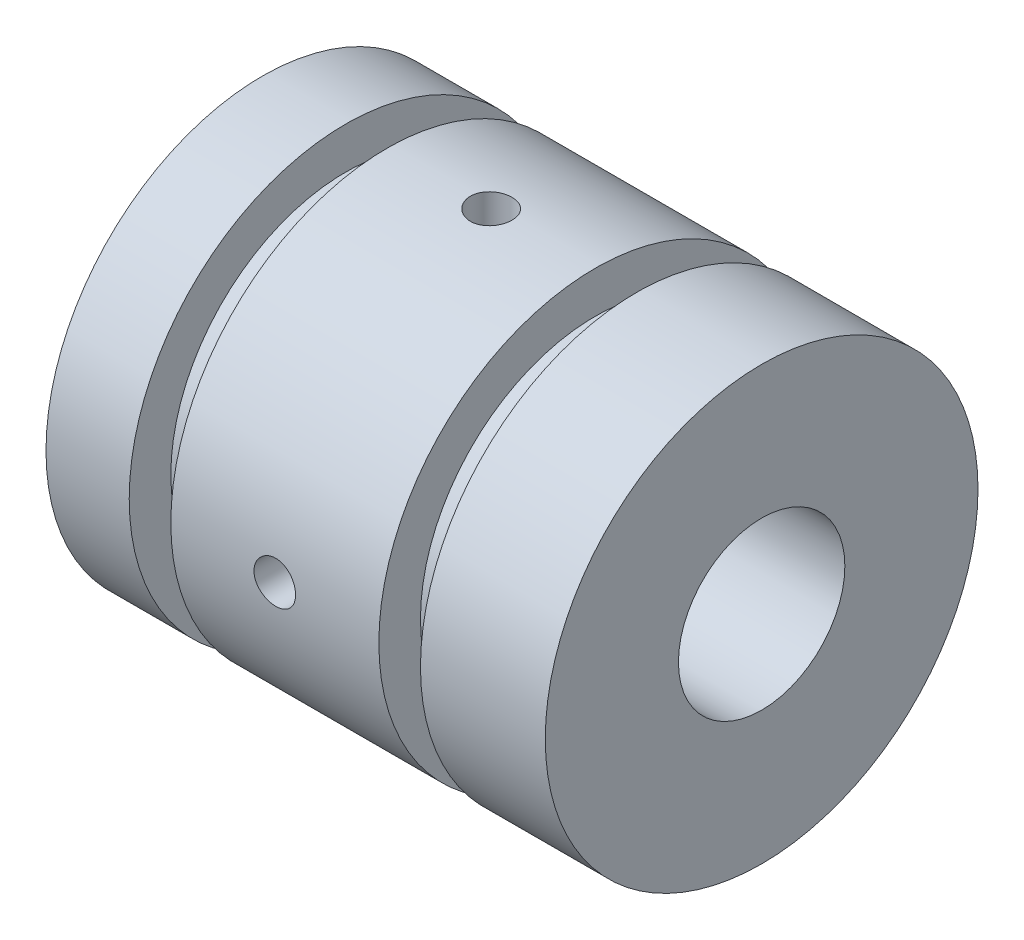
SolidWorks part; units mm, degrees
ref_plane "Front Plane" through (0, 0, 0) normal (0, 0, 1) x (1, 0, 0)
ref_plane "Top Plane" through (0, 0, 0) normal (0, 1, 0) x (1, 0, 0)
ref_plane "Right Plane" through (0, 0, 0) normal (1, 0, 0) x (0, 0, -1)
sketch "Sketch1" plane through (0, 0, 0) normal (0, 0, 1) x (1, 0, 0)
  line L0 (0, 0) -> (0, 26)
  line L1 (0, 26) -> (10, 26)
  line L2 (10, 26) -> (10, 21)
  line L3 (10, 21) -> (15, 21)
  line L4 (15, 21) -> (15, 26)
  line L5 (15, 26) -> (40, 26)
  line L6 (40, 26) -> (40, 21)
  line L7 (40, 21) -> (45, 21)
  line L8 (45, 21) -> (45, 26)
  line L9 (45, 26) -> (60, 26)
  line L10 (60, 26) -> (60, 45)
  line L11 (60, 45) -> (80, 45)
  line L12 (80, 45) -> (80, 0)
  line L13 (80, 0) -> (0, 0)
  line L14 (0, 0) -> (192.5132, 0) construction
  dimension "D1" = 80
  dimension "D2" = 26
  dimension "D3" = 10
  dimension "D4" = 25
  dimension "D5" = 15
  dimension "D6" = 5
  dimension "D7" = 45
  dimension "D8" = 5
revolve "Revolve1" add sketch "Sketch1" angle 360 about L14
sketch "Sketch2" plane through (0, 0, 0) normal (-1, 0, 0) x (0, 0, 1)
  circle A0 centre (0, 0) radius 20
  dimension "D1" = 40
extrude "Cut-Extrude2" cut sketch "Sketch2" against normal blind 10
hole_wizard "1/8 (0.125) Diameter Hole1" positions "Sketch4" profile "Sketch5" hole size "1/8" standard "ANSI Inch"
sketch "Sketch4" plane through (10, 0, 0) normal (-1, 0, 0) x (0, 0, 1)
  point P0 (15.1447, 0)
  point P6 (0.1447, -15)
  point P7 (-14.8553, 0)
  point P8 (0.1447, 15)
  point P9 (0, 0)
  dimension "D2" = 15
  dimension "D1" = 4
sketch "Sketch5" plane through (10, 0, 15.1447) normal (0, 1, 0) x (0, 0, 1)
  line L0 (0, 0) -> (0, 7.9539)
  line L1 (0, 7.9539) -> (1.5875, 7)
  line L2 (1.5875, 7) -> (1.5875, 0)
  line L5 (1.5875, 0) -> (0, 0)
  line L10 (0, 7.9539) -> (-1.5875, 7) construction
  line L11 (0, -6.35) -> (0, 107.95) construction
  dimension "Hole Dia." = 3.175
  dimension "Hole Depth" = 7
  dimension "Drill Angle" = 118
sketch "Sketch6" plane through (10, 0, 0) normal (-1, 0, 0) x (0, 0, 1)
  circle A0 centre (0, 0) radius 10
  dimension "D1" = 20
extrude "Cut-Extrude3" cut sketch "Sketch6" against normal blind 50
ref_axis "Axis1" through (40, 0, 0) along (-1, 0, 0)
ref_plane "Plane1" through (0, 0, 26) normal (0, 0, 1) x (1, 0, 0)
hole_wizard "1/2 (0.5) Diameter Hole1" positions "Sketch8" profile "Sketch9" hole size "1/2" standard "ANSI Inch" end condition up to next
sketch "Sketch8" plane through (80, 0, 0) normal (1, 0, 0) x (0, 0, -1)
  point P0 (0, 0)
sketch "Sketch9" plane through (80, 0, 0) normal (0, 1, 0) x (0, 0, -1)
  line L0 (0, 0) -> (0, 20)
  line L1 (0, 20) -> (6.35, 20)
  line L2 (6.35, 20) -> (6.35, 0)
  line L5 (6.35, 0) -> (0, 0)
  line L11 (0, -6.35) -> (0, 107.95) construction
  dimension "Thru Hole Dia." = 12.7
  dimension "Thru Hole Depth" = 20
sketch "Sketch10" plane through (0, -26, 26) normal (0, 0, 1) x (1, 0, 0)
  line L0 (15, 47) -> (15, 5) construction
  line L1 (40, 26) -> (15, 26) construction
  circle A0 centre (27.4918, 26) radius 2.5
  dimension "D1" = 5
  dimension "D2" = 12.4918
extrude "Cut-Extrude8" cut sketch "Sketch10" against normal blind 5
ref_plane "Plane2" through (0, 0, -26) normal (0, 0, -1) x (-1, 0, 0)
sketch "Sketch11" plane through (0, 0, -26) normal (0, 0, -1) x (-1, 0, 0)
  line L0 (-40, 0) -> (-15, 0) construction
  line L1 (-15, -26) -> (-15, 26) construction
  circle A0 centre (-27.5, 0) radius 2.5
  dimension "D1" = 5
  dimension "D2" = 12.5
extrude "Cut-Extrude9" cut sketch "Sketch11" against normal blind 5
ref_plane "Plane3" through (0, -26, 0) normal (0, -1, 0) x (-1, 0, 0)
sketch "Sketch12" plane through (0, -26, 0) normal (0, -1, 0) x (-1, 0, 0)
  line L0 (-40, 0) -> (-15, 0) construction
  line L1 (-15, -21) -> (-15, 21) construction
  circle A0 centre (-27.5, 0) radius 2.5
  dimension "D1" = 12.5
  dimension "D2" = 5
extrude "Cut-Extrude10" cut sketch "Sketch12" against normal blind 5
ref_plane "Plane4" through (0, 26, 0) normal (0, 1, 0) x (1, 0, 0)
sketch "Sketch13" plane through (0, -21, 0) normal (0, -1, 0) x (-1, 0, 0)
  line L0 (-40, 0) -> (-15, 0) construction
  line L1 (-15, -26) -> (-15, 26) construction
  circle A0 centre (-27.5, 0) radius 2.5
  dimension "D1" = 5
  dimension "D2" = 12.5
extrude "Cut-Extrude11" cut sketch "Sketch13" against normal blind 5
sketch "Sketch14" plane through (0, 26, 0) normal (0, 1, 0) x (1, 0, 0)
  line L0 (40, 0) -> (15, 0) construction
  line L1 (15, 26) -> (15, -26) construction
  circle A0 centre (27.5, 0) radius 2.5
  dimension "D1" = 5
  dimension "D2" = 12.5
extrude "Cut-Extrude12" cut sketch "Sketch14" against normal blind 5
sketch "Sketch15" plane through (80, 0, 0) normal (1, 0, 0) x (0, 0, -1)
  circle A0 centre (0, -35) radius 5
  circle A1 centre (-35, 0) radius 5
  circle A2 centre (0, 35) radius 5
  circle A3 centre (35, 0) radius 5
  point P13 (0, 0)
  dimension "D1" = 10
  dimension "D2" = 35
  dimension "D3" = 4
extrude "Cut-Extrude13" cut sketch "Sketch15" against normal through all
sketch "Sketch16" plane through (80, 0, 0) normal (1, 0, 0) x (0, 0, -1)
  circle A0 centre (0, 0) radius 45
extrude "Cut-Extrude14" cut sketch "Sketch16" against normal blind 20
hole_wizard "1/8 (0.125) Diameter Hole2" positions "Sketch18" profile "Sketch19" hole size "1/8" standard "ANSI Inch"
sketch "Sketch18" plane through (0, 0, 0) normal (-1, 0, 0) x (0, 0, 1)
  point P0 (0, 23)
  point P10 (23, 0)
  point P11 (0, -23)
  point P12 (-23, 0)
  point P14 (0, 0)
  dimension "D2" = 23
  dimension "D1" = 4
sketch "Sketch19" plane through (0, 23, 0) normal (0, 1, 0) x (0, 0, 1)
  line L0 (0, 0) -> (0, 7.9539)
  line L1 (0, 7.9539) -> (1.5875, 7)
  line L2 (1.5875, 7) -> (1.5875, 0)
  line L5 (1.5875, 0) -> (0, 0)
  line L10 (0, 7.9539) -> (-1.5875, 7) construction
  line L11 (0, -6.35) -> (0, 107.95) construction
  dimension "Hole Dia." = 3.175
  dimension "Hole Depth" = 7
  dimension "Drill Angle" = 118
